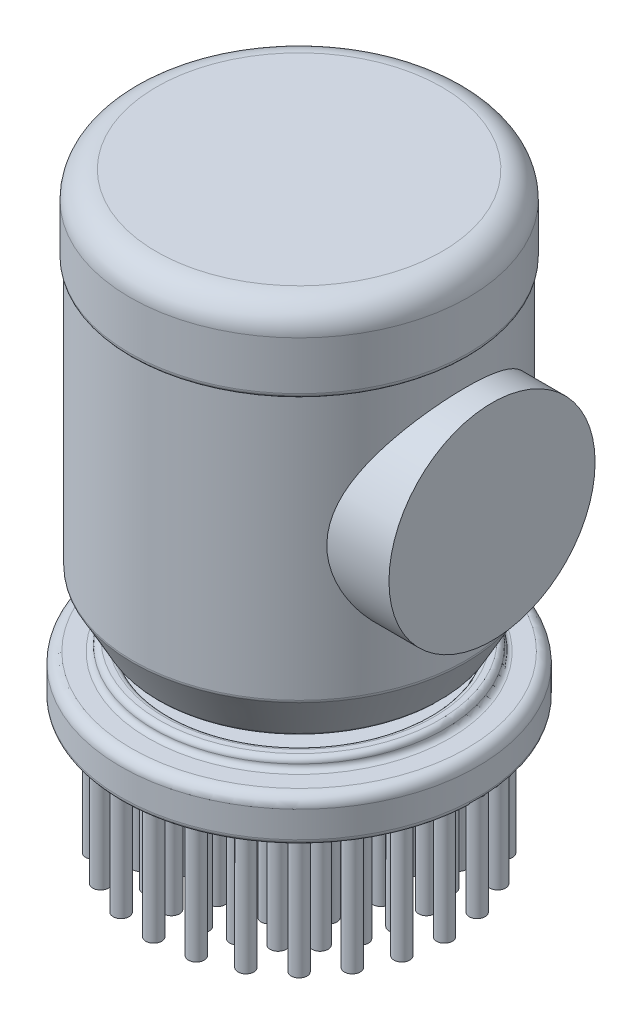
SolidWorks part; units mm, degrees
ref_plane "Front Plane" through (0, 0, 0) normal (0, 0, 1) x (1, 0, 0)
ref_plane "Top Plane" through (0, 0, 0) normal (0, 1, 0) x (1, 0, 0)
ref_plane "Right Plane" through (0, 0, 0) normal (1, 0, 0) x (0, 0, -1)
sketch "Sketch1" plane through (0, 0, 0) normal (0, 0, 1) x (1, 0, 0)
  line L0 (26.5, 0) -> (31.5, 9)
  line L1 (0, 0) -> (31.5, 0)
  line L2 (0, 0) -> (0, 74)
  line L3 (0, 74) -> (31.5, 74)
  line L4 (31.5, 0) -> (31.5, 74)
  line L6 (0, 0) -> (1.5, 0)
  line L7 (0, 0) -> (0, -3)
  line L8 (0, -3) -> (1.5, -3)
  line L9 (1.5, 0) -> (1.5, -3)
  line L10 (0, -3) -> (27.5, -3)
  line L11 (0, -3) -> (0, -5)
  line L12 (0, -5) -> (27.5, -5)
  line L13 (27.5, -3) -> (27.5, -5)
  line L14 (0, -5) -> (33.75, -5)
  line L15 (0, -5) -> (0, -13)
  line L16 (0, -13) -> (33.75, -13)
  line L17 (33.75, -5) -> (33.75, -13)
  dimension "D1" = 31.5
  dimension "D2" = 26.5
  dimension "D3" = 74
  dimension "D4" = 9
  dimension "D5" = 3
  dimension "D6" = 1.5
  dimension "D7" = 27.5
  dimension "D8" = 2
  dimension "D9" = 33.75
  dimension "D10" = 8
revolve "Revolve1" add sketch "Sketch1" angle 360 about L2 region at (15.6127, 37.3314, 0) region at (0.75, -1.5, 0) region at (13.75, -4, 0) region at (16.875, -9, 0)
sketch "Sketch2" plane through (0, -3, 0) normal (0, 1, 0) x (1, 0, 0)
  circle A0 centre (0, 0) radius 24.5
  circle A2 centre (0, 0) radius 13
  circle A3 centre (0, 0) radius 27.5 construction
  dimension "D1" = 3
  dimension "D2" = 26
extrude "Cut-Extrude2" cut sketch "Sketch2" against normal blind 2
sketch "Sketch3" plane through (0, 74, 0) normal (0, 1, 0) x (1, 0, 0)
  circle A0 centre (0, 0) radius 32
  dimension "D1" = 64
extrude "Boss-Extrude1" add sketch "Sketch3" against normal blind 15
sketch "Sketch4" plane through (0, -13, 0) normal (0, -1, 0) x (1, 0, 0)
  line L0 (0, 27.5) -> (0, 0) construction
  line L1 (0, 0) -> (7.1175, 26.563) construction
  line L2 (3.5895, 27.2647) -> (0, 0) construction
  line L3 (0, 21.6855) -> (2.8063, 21.3161)
  line L4 (2.8063, 21.3161) -> (5.6126, 20.9466)
  line L5 (0, 0) -> (2.8063, 21.3161) construction
  line L6 (0, 0) -> (8.2277, 19.8634) construction
  circle A0 centre (0, 0) radius 27.5 construction
  circle A1 centre (0, 27.5) radius 1.5
  circle A2 centre (0, 0) radius 21.5 construction
  circle A3 centre (0, 0) radius 15.5 construction
  circle A4 centre (0, 15.5) radius 1.5
  circle A5 centre (7.1175, 26.563) radius 1.5
  circle A6 centre (13.75, 23.8157) radius 1.5
  circle A7 centre (19.4454, 19.4454) radius 1.5
  circle A8 centre (23.8157, 13.75) radius 1.5
  circle A9 centre (26.563, 7.1175) radius 1.5
  circle A10 centre (27.5, 0) radius 1.5
  circle A11 centre (26.563, -7.1175) radius 1.5
  circle A12 centre (23.8157, -13.75) radius 1.5
  circle A13 centre (19.4454, -19.4454) radius 1.5
  circle A14 centre (13.75, -23.8157) radius 1.5
  circle A15 centre (7.1175, -26.563) radius 1.5
  circle A16 centre (0, -27.5) radius 1.5
  circle A17 centre (-7.1175, -26.563) radius 1.5
  circle A18 centre (-13.75, -23.8157) radius 1.5
  circle A19 centre (-19.4454, -19.4454) radius 1.5
  circle A20 centre (-23.8157, -13.75) radius 1.5
  circle A21 centre (-26.563, -7.1175) radius 1.5
  circle A22 centre (-27.5, 0) radius 1.5
  circle A23 centre (-26.563, 7.1175) radius 1.5
  circle A24 centre (-23.8157, 13.75) radius 1.5
  circle A25 centre (-19.4454, 19.4454) radius 1.5
  circle A26 centre (2.8063, 21.3161) radius 1.5
  circle A27 centre (0, 0) radius 9.5 construction
  circle A28 centre (-13.75, 23.8157) radius 1.5
  circle A29 centre (-7.1175, 26.563) radius 1.5
  circle A30 centre (8.2277, 19.8634) radius 1.5
  circle A31 centre (13.0884, 17.0571) radius 1.5
  circle A32 centre (17.0571, 13.0884) radius 1.5
  circle A33 centre (19.8634, 8.2277) radius 1.5
  circle A34 centre (21.3161, 2.8063) radius 1.5
  circle A35 centre (21.3161, -2.8063) radius 1.5
  circle A36 centre (19.8634, -8.2277) radius 1.5
  circle A37 centre (17.0571, -13.0884) radius 1.5
  circle A38 centre (13.0884, -17.0571) radius 1.5
  circle A39 centre (8.2277, -19.8634) radius 1.5
  circle A40 centre (2.8063, -21.3161) radius 1.5
  circle A41 centre (-2.8063, -21.3161) radius 1.5
  circle A42 centre (-8.2277, -19.8634) radius 1.5
  circle A43 centre (-13.0884, -17.0571) radius 1.5
  circle A44 centre (-17.0571, -13.0884) radius 1.5
  circle A45 centre (-19.8634, -8.2277) radius 1.5
  circle A46 centre (-21.3161, -2.8063) radius 1.5
  circle A47 centre (-21.3161, 2.8063) radius 1.5
  circle A48 centre (-19.8634, 8.2277) radius 1.5
  circle A49 centre (-17.0571, 13.0884) radius 1.5
  circle A50 centre (-13.0884, 17.0571) radius 1.5
  circle A51 centre (-8.2277, 19.8634) radius 1.5
  circle A52 centre (-2.8063, 21.3161) radius 1.5
  circle A53 centre (4.0117, 14.9719) radius 1.5
  circle A54 centre (7.75, 13.4234) radius 1.5
  circle A55 centre (10.9602, 10.9602) radius 1.5
  circle A56 centre (13.4234, 7.75) radius 1.5
  circle A57 centre (14.9719, 4.0117) radius 1.5
  circle A58 centre (15.5, 0) radius 1.5
  circle A59 centre (14.9719, -4.0117) radius 1.5
  circle A60 centre (13.4234, -7.75) radius 1.5
  circle A61 centre (10.9602, -10.9602) radius 1.5
  circle A62 centre (7.75, -13.4234) radius 1.5
  circle A63 centre (4.0117, -14.9719) radius 1.5
  circle A64 centre (0, -15.5) radius 1.5
  circle A65 centre (-4.0117, -14.9719) radius 1.5
  circle A66 centre (-7.75, -13.4234) radius 1.5
  circle A67 centre (-10.9602, -10.9602) radius 1.5
  circle A68 centre (-13.4234, -7.75) radius 1.5
  circle A69 centre (-14.9719, -4.0117) radius 1.5
  circle A70 centre (-15.5, 0) radius 1.5
  circle A71 centre (-14.9719, 4.0117) radius 1.5
  circle A72 centre (-13.4234, 7.75) radius 1.5
  circle A73 centre (-10.9602, 10.9602) radius 1.5
  circle A74 centre (-7.75, 13.4234) radius 1.5
  circle A75 centre (-4.0117, 14.9719) radius 1.5
  point P54 (0, 0)
  point P159 (0, 0)
  dimension "D1" = 6
  dimension "60" = 55
  dimension "D2" = 3
  dimension "D3" = 6
  dimension "D4" = 3
  dimension "D6" = 3
  dimension "D7" = 6
  dimension "D9" = 15
  dimension "D5" = 24
  dimension "D8" = 24
  dimension "D10" = 24
extrude "Boss-Extrude2" add sketch "Sketch4" along normal blind 25 contours A10 | A9 | A8 | A7 | A6 | A5 | A1 | A29 | A28 | A25 | A24 | A23 | A22 | A21 | A20 | A19 | A18 | A16 | A15 | A14 | A13 | A12 | A11 | A52 | A51 | A50 | A49 | A48 | A47 | A46 | A45 | A44 | A43 | A42 | A41 | A40 | A39 | A37 | A35 | A34 | A33 | A30 | L4 A26 L3 | L3 A26 L4 | A4 | A53 | A54 | A55 | A56 | A57 | A58 | A59 | A60 | A61 | A63 | A64 | A65 | A66 | A67 | A68 | A69 | A70 | A75 | A74 | A73 | A72 | A71 | A17 | A38 | A36 | A32 | A31 | A62 region at (2.8894, -13, 21.9472) region at (2.7232, -13, 20.6849) region at (0, -13, 27.5) region at (0, -13, 15.5) region at (7.1175, -13, 26.563) region at (13.75, -13, 23.8157) region at (19.4454, -13, 19.4454) region at (23.8157, -13, 13.75) region at (26.563, -13, 7.1175) region at (27.5, -13, 0) region at (26.563, -13, -7.1175) region at (23.8157, -13, -13.75) region at (19.4454, -13, -19.4454) region at (13.75, -13, -23.8157) region at (7.1175, -13, -26.563) region at (0, -13, -27.5) region at (-13.75, -13, -23.8157) region at (-19.4454, -13, -19.4454) region at (-23.8157, -13, -13.75) region at (-26.563, -13, -7.1175) region at (-27.5, -13, 0) region at (-26.563, -13, 7.1175) region at (-23.8157, -13, 13.75) region at (-19.4454, -13, 19.4454) region at (-13.75, -13, 23.8157) region at (-7.1175, -13, 26.563) region at (8.2277, -13, 19.8634) region at (19.8634, -13, 8.2277) region at (21.3161, -13, 2.8063) region at (21.3161, -13, -2.8063) region at (17.0571, -13, -13.0884) region at (8.2277, -13, -19.8634) region at (2.8063, -13, -21.3161) region at (-2.8063, -13, -21.3161) region at (-8.2277, -13, -19.8634) region at (-13.0884, -13, -17.0571) region at (-17.0571, -13, -13.0884) region at (-19.8634, -13, -8.2277) region at (-21.3161, -13, -2.8063) region at (-21.3161, -13, 2.8063) region at (-19.8634, -13, 8.2277) region at (-17.0571, -13, 13.0884) region at (-13.0884, -13, 17.0571) region at (-8.2277, -13, 19.8634) region at (-2.8063, -13, 21.3161) region at (4.0117, -13, 14.9719) region at (7.75, -13, 13.4234) region at (10.9602, -13, 10.9602) region at (13.4234, -13, 7.75) region at (14.9719, -13, 4.0117) region at (15.5, -13, 0) region at (14.9719, -13, -4.0117) region at (13.4234, -13, -7.75) region at (10.9602, -13, -10.9602) region at (4.0117, -13, -14.9719) region at (0, -13, -15.5) region at (-4.0117, -13, -14.9719) region at (-7.75, -13, -13.4234) region at (-10.9602, -13, -10.9602) region at (-13.4234, -13, -7.75)
fillet "Fillet1" radius 5 1 edges at (0, 74, 32)
fillet "Fillet2" radius 1 7 edges at (0, -3, 24.5) (0, -3, -27.5) (0, -13, -33.75) (0, -5, -27.5) (0, 0, -26.5) (0, 9, -31.5) (0, 59, 32)
fillet "Fillet3" radius 2 1 edges at (0, -5, -33.75)
sketch "Sketch5" plane through (0, 0, 0) normal (1, 0, 0) x (0, 0, -1)
  line L0 (27, 74) -> (-27, 74) construction
  circle A0 centre (0, 34.5) radius 19.5
  dimension "D1" = 39
  dimension "D2" = 39.5
extrude "Boss-Extrude3" add sketch "Sketch5" along normal blind 36.5
